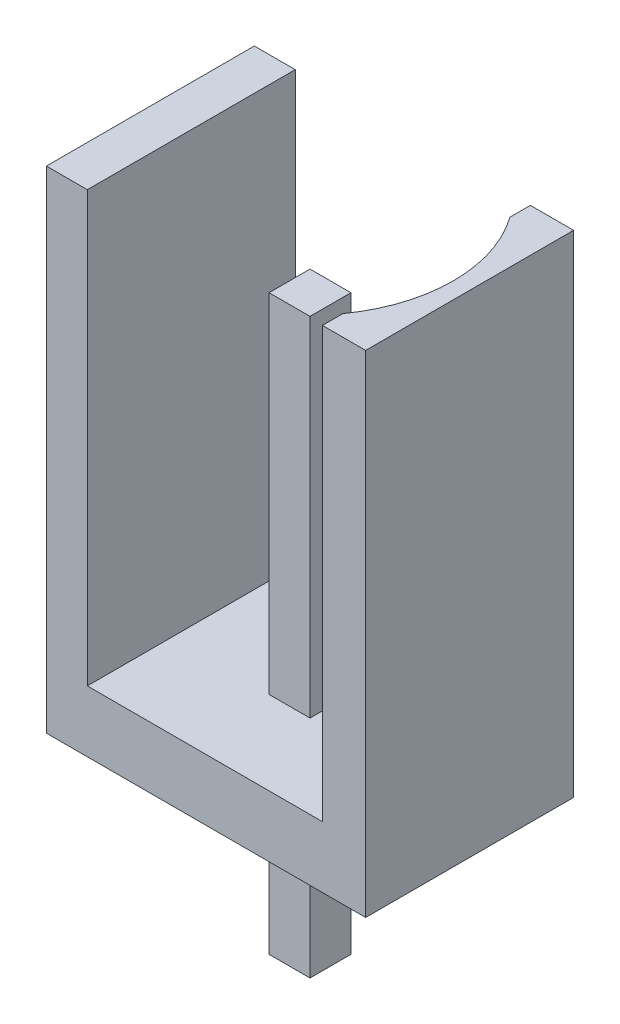
SolidWorks part; units mm, degrees
ref_plane "前视基准面" through (0, 0, 0) normal (0, 0, 1) x (1, 0, 0)
ref_plane "上视基准面" through (0, 0, 0) normal (0, 1, 0) x (1, 0, 0)
ref_plane "右视基准面" through (0, 0, 0) normal (1, 0, 0) x (0, 0, -1)
sketch "草图1" plane through (0, 0, 0) normal (0, 1, 0) x (1, 0, 0)
  line L0 (0, 11.3571) -> (0, -8.6742) construction
  line L1 (-3.9, 2.54) -> (3.9, 2.54)
  line L2 (-3.9, 2.54) -> (-3.9, -2.54)
  line L3 (-3.9, -2.54) -> (3.9, -2.54)
  line L4 (3.9, 2.54) -> (3.9, -2.54)
  line L5 (-11.8577, 0) -> (16.1453, 0) construction
  dimension "D1" = 7.8
  dimension "D2" = 5.08
extrude "拉伸1" add sketch "草图1" along normal blind 12
sketch "草图2" plane through (0, 12, 0) normal (0, 1, 0) x (-1, 0, 0)
  line L0 (-6.731, 0) -> (5.6712, 0) construction
  line L1 (0, 4.6677) -> (0, -4.2437) construction
  line L2 (-4.9856, 2.04) -> (6.376, 2.04) construction
  line L5 (3.9, 2.54) -> (-3.9, 2.54) construction
  line L6 (-4.9856, -2.04) -> (6.376, -2.04) construction
  line L7 (-2.844, 2.04) -> (-2.844, 2.54)
  line L8 (-2.844, -2.04) -> (-2.844, -2.54)
  line L10 (-3.9, -2.54) -> (3.9, -2.54) construction
  line L11 (2.9, 2.54) -> (2.9, -2.54)
  line L12 (3.9, -2.54) -> (3.9, 2.54) construction
  line L13 (-2.844, 2.54) -> (2.9, 2.54)
  line L14 (-2.844, -2.54) -> (2.9, -2.54)
  arc A0 (-2.844, 2.04) -> (-2.844, -2.04) centre (0, 0) ccw
  dimension "D1" = 0.5
  dimension "D2" = 3.5
  dimension "D3" = 1
extrude "切除-拉伸1" cut sketch "草图2" against normal offset from surface (10.5 mm away) 1.5 up to face at (0, 0, 0)
sketch "草图4" plane through (0, 0, 0) normal (0, -1, 0) x (1, 0, 0)
  line L0 (0, 0.6646) -> (0, -0.6904) construction
  line L1 (-0.5, 0.5) -> (0.5, 0.5)
  line L2 (-0.5, 0.5) -> (-0.5, -0.5)
  line L3 (-0.5, -0.5) -> (0.5, -0.5)
  line L4 (0.5, 0.5) -> (0.5, -0.5)
  line L5 (-0.4955, 0) -> (0.6276, 0) construction
  dimension "D1" = 1
  dimension "D2" = 1
extrude "凸台-拉伸1" add sketch "草图4" along normal blind 4 and the other way blind 10
